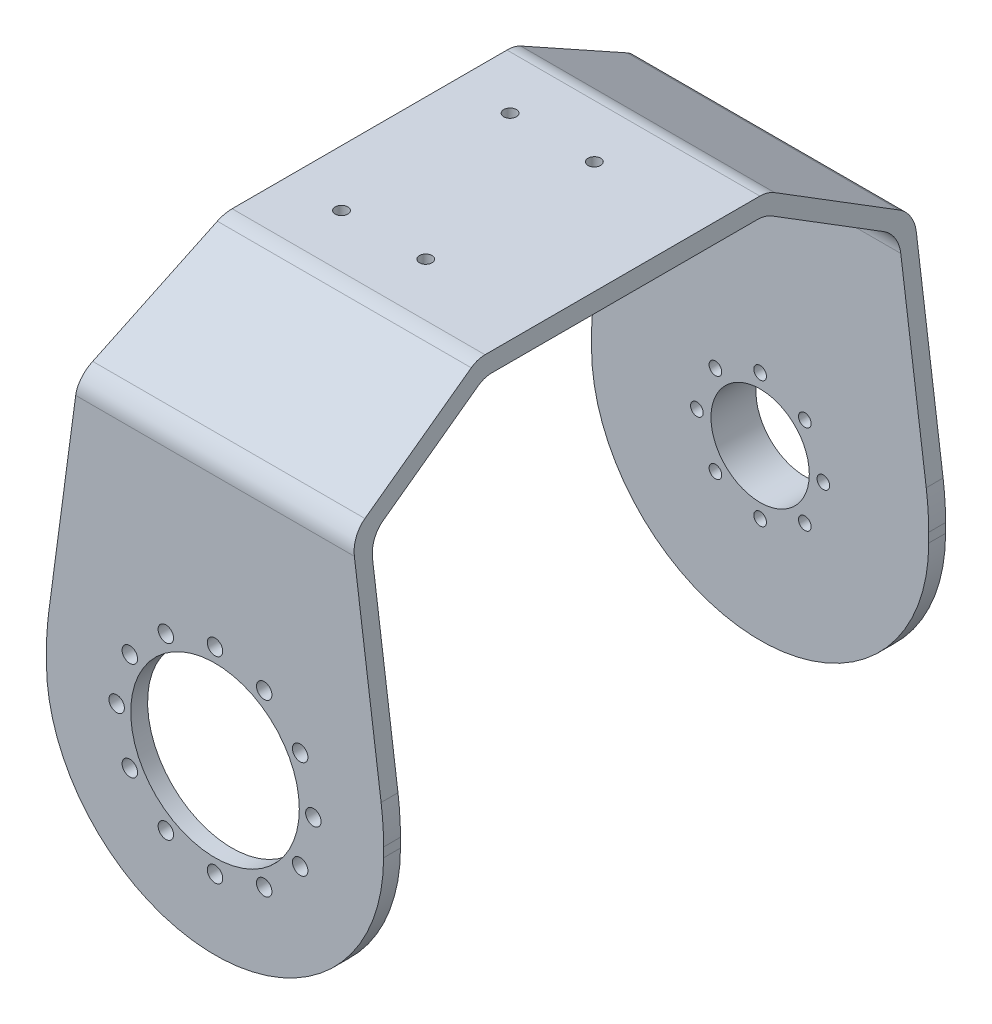
SolidWorks part; units mm, degrees
ref_plane "前视基准面" through (0, 0, 0) normal (0, 0, 1) x (1, 0, 0)
ref_plane "上视基准面" through (0, 0, 0) normal (0, 1, 0) x (1, 0, 0)
ref_plane "右视基准面" through (0, 0, 0) normal (1, 0, 0) x (0, 0, -1)
other "Configuration Table"
sketch "草图11" plane through (0, 0, 0) normal (1, 0, 0) x (0, 0, -1)
  line L0 (0, 0) -> (0, 82.4039) construction
  line L1 (-50, 206) -> (50, 206)
  line L2 (50, 206) -> (94, 180)
  line L3 (94, 180) -> (94, 0)
  line L4 (-94, 180) -> (-94, 0)
  line L5 (-50, 206) -> (-94, 180)
  point P10 (0, 206)
  dimension "D1" = 94
  dimension "D2" = 180
  dimension "D3" = 100
  dimension "D4" = 206
extrude "拉伸-薄壁1" add sketch "草图11" along normal blind 180 thin thin type one direction wall 6
sketch "草图12" plane through (0, 0, 0) normal (0, 0, 1) x (1, 0, 0)
  line L0 (90, 283.6741) -> (90, -81.1896) construction
  line L1 (180, 183.4238) -> (180, 0) construction
  line L2 (0, 183.4238) -> (0, 0) construction
  line L4 (180, 212) -> (0, 212) construction
  line L5 (0, 0) -> (0, 212)
  line L6 (0, 212) -> (0, 183.4238) construction
  line L7 (0, 212) -> (45, 212)
  line L12 (180, 0) -> (0, 0) construction
  line L13 (30, 0) -> (0, 0)
  line L14 (150, 0) -> (180, 0)
  line L15 (180, 0) -> (180, 212)
  line L16 (180, 212) -> (135, 212)
  line L18 (45, 212) -> (30, 100)
  line L19 (30, 100) -> (30, 0)
  line L20 (150, 100) -> (150, 0)
  line L21 (135, 212) -> (150, 100)
  circle A0 centre (90, 90) radius 45 construction
  dimension "D1" = 90
  dimension "D2" = 90
  dimension "D3" = 90
  dimension "D4" = 100
  dimension "D5" = 30
extrude "切除-拉伸1" cut sketch "草图12" against normal through all both and the other way through all
sketch "草图14" plane through (0, 0, 100) normal (0, 0, 1) x (1, 0, 0)
  line L0 (90, 90) -> (90, 146.2724) construction
  line L1 (90, 283.6741) -> (90, -81.1896) construction
  circle A0 centre (90, 90) radius 30
  circle A2 centre (90, 90) radius 35 construction
  circle A11 centre (90, 125) radius 2.75
  circle A12 centre (107.5, 120.3109) radius 2.75
  circle A13 centre (120.3109, 107.5) radius 2.75
  circle A14 centre (125, 90) radius 2.75
  circle A15 centre (120.3109, 72.5) radius 2.75
  circle A16 centre (107.5, 59.6891) radius 2.75
  circle A17 centre (90, 55) radius 2.75
  circle A18 centre (72.5, 59.6891) radius 2.75
  circle A19 centre (59.6891, 72.5) radius 2.75
  circle A20 centre (55, 90) radius 2.75
  circle A21 centre (59.6891, 107.5) radius 2.75
  circle A22 centre (72.5, 120.3109) radius 2.75
  point P26 (90, 90)
  point P35 (90, 90)
  dimension "D1" = 60
  dimension "D2" = 70
  dimension "D3" = 5.5
  dimension "D4" = 12
extrude "切除-拉伸3" cut sketch "草图14" against normal blind 50
sketch "草图15" plane through (0, 0, -100) normal (0, 0, -1) x (-1, 0, 0)
  circle A0 centre (-90, 90) radius 27.5
  dimension "D1" = 55
extrude "凸台-拉伸3" add sketch "草图15" along normal blind 10
sketch "草图16" plane through (0, 0, -110) normal (0, 0, -1) x (-1, 0, 0)
  line L0 (-90, 90) -> (-36.3801, 90) construction
  line L1 (-90, 90) -> (-90, 130.4972) construction
  line L2 (-90, 283.6741) -> (-90, -81.1896) construction
  circle A0 centre (-90, 90) radius 17.5
  circle A1 centre (-67.5, 90) radius 2.25
  circle A2 centre (-74.0901, 74.0901) radius 2.25
  circle A3 centre (-90, 67.5) radius 2.25
  circle A4 centre (-105.9099, 74.0901) radius 2.25
  circle A5 centre (-112.5, 90) radius 2.25
  circle A6 centre (-105.9099, 105.9099) radius 2.25
  circle A7 centre (-90, 112.5) radius 2.25
  circle A8 centre (-74.0901, 105.9099) radius 2.25
  point P25 (-90, 90)
  dimension "D1" = 35
  dimension "D2" = 4.5
  dimension "D3" = 22.5
  dimension "D4" = 8
extrude "切除-拉伸4" cut sketch "草图16" against normal blind 32.5
sketch "草图17" plane through (0, 212, 0) normal (0, 1, 0) x (1, 0, 0)
  line L0 (25.9225, 0) -> (174.1323, 0) construction
  line L1 (90, -121.1832) -> (90, 132.8572) construction
  line L2 (135, 51.6402) -> (135, -51.6402) construction
  line L3 (45, 51.6402) -> (45, -51.6402) construction
  line L4 (80, 115.4484) -> (80, -112.8417) construction
  circle A0 centre (95, 30) radius 2.25
  circle A1 centre (95, -30) radius 2.25
  circle A2 centre (65, -30) radius 2.25
  circle A3 centre (65, 30) radius 2.25
  dimension "D1" = 4.5
  dimension "D2" = 60
  dimension "D3" = 30
  dimension "D4" = 10
extrude "切除-拉伸5" cut sketch "草图17" against normal up to surface (6 mm away) up to face at (90, 206, 0)
fillet "圆角1" radius 100 4 edges at (30, 100, -97) (30, 100, 97) (150, 100, 97) (150, 100, -97)
fillet "圆角2" radius 55 4 edges at (30, 0, 97) (150, 0, 97) (150, 0, -97) (30, 0, -97)
fillet "圆角3" radius 10 8 edges at (90, 180, -94) (90, 180, 94) (90, 206, 50) (90, 206, -50) (90, 183.4238, -100) (90, 212, -51.6402) (90, 212, 51.6402) (90, 183.4238, 100)
sketch "草图18" plane through (0, 0, 100) normal (0, 0, 1) x (1, 0, 0)
  line L0 (150, 93.3333) -> (150, 55) construction
  line L1 (95, 0) -> (85, 0) construction
  line L2 (30, 55) -> (30, 93.3333) construction
  line L3 (150, 90) -> (150, 55)
  line L4 (95, 0) -> (85, 0)
  line L5 (30, 55) -> (30, 90)
  arc A0 (30, 90) -> (150, 90) centre (90, 90) ccw
  arc A1 (95, 0) -> (150, 55) centre (95, 55) ccw construction
  arc A2 (30, 55) -> (85, 0) centre (85, 55) ccw construction
  arc A3 (95, 0) -> (150, 55) centre (95, 55) ccw
  arc A4 (30, 55) -> (85, 0) centre (85, 55) ccw
extrude "切除-拉伸6" cut sketch "草图18" against normal blind 320
